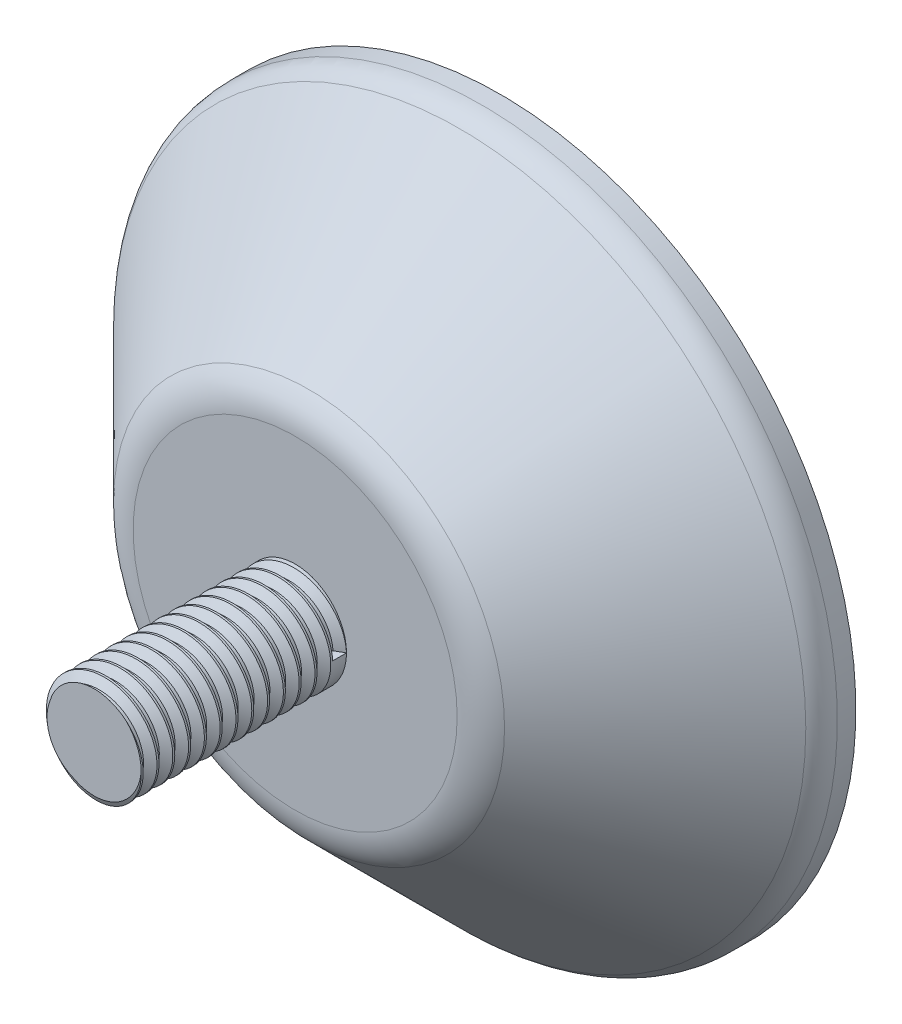
SolidWorks part; units mm, degrees
ref_plane "Front Plane" through (0, 0, 0) normal (0, 0, 1) x (1, 0, 0)
ref_plane "Top Plane" through (0, 0, 0) normal (0, 1, 0) x (1, 0, 0)
ref_plane "Right Plane" through (0, 0, 0) normal (1, 0, 0) x (0, 0, -1)
sketch "Sketch1" plane through (0, 0, 0) normal (0, 0, 1) x (1, 0, 0)
  circle A0 centre (0, 0) radius 22.5
  dimension "D1" = 45
extrude "Boss-Extrude1" add sketch "Sketch1" along normal blind 13
sketch "Sketch2" plane through (0, 0, 13) normal (0, 0, 1) x (1, 0, 0)
  circle A0 centre (0, 0) radius 3.25
  dimension "D1" = 6.5
extrude "Boss-Extrude2" add sketch "Sketch2" along normal blind 13
chamfer "Chamfer1" distance 11 angle 45 1 edges at (22.5, 0, 13)
thread "Thread1" pitch 1 method cut profile "Thread Profile1" start angle 0, offset 0, length 15, pitch 1, diameter 6.5
ref_plane "Plane1" through (3.25, 0, 13) normal (0, -1, 0) x (1, 0, 0)
sketch "Thread Profile1" plane through (3.25, 0, 13) normal (0, -1, 0) x (1, 0, 0)
  line L0 (0, 0) -> (0, 1) construction
  line L11 (0, 0) -> (0, 0.875)
  line L12 (0, 0.875) -> (-0.5413, 0.5625)
  line L13 (-0.5413, 0.5625) -> (-0.5413, 0.3125)
  line L15 (-0.5413, 0.3125) -> (0, 0)
  line L17 (-0.5413, 0.4375) -> (0, 0.4375) construction
  point P2 (0, 0)
  dimension "Pitch" = 1
  dimension "Profile_Angle" = 60
  dimension "Profile_Land" = 0.25
  dimension "Profile_Height" = 0.5413
fillet "Fillet2" radius 3 1 edges at (11.5, 0, 13)
fillet "Fillet3" radius 2 1 edges at (22.5, 0, 2)
